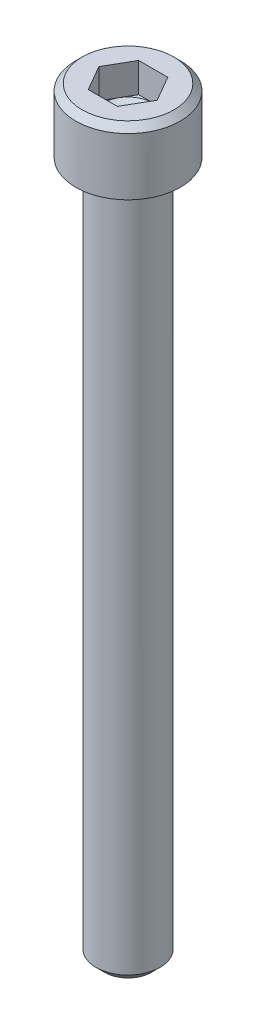
SolidWorks part; units mm, degrees
material "Alloy Steel"
ref_plane "Front Plane" through (0, 0, 0) normal (0, 0, 1) x (1, 0, 0)
ref_plane "Top Plane" through (0, 0, 0) normal (0, 1, 0) x (1, 0, 0)
ref_plane "Right Plane" through (0, 0, 0) normal (1, 0, 0) x (0, 0, -1)
sketch "Sketch1" plane through (0, 0, 0) normal (0, 0, 1) x (1, 0, 0)
  line L0 (2.8702, 3.5052) -> (0, 3.5052)
  line L1 (0, 3.5052) -> (0, 0)
  line L2 (0, 0) -> (2.8702, 0)
  line L3 (2.8702, 0) -> (2.8702, 3.5052)
  line L4 (0, 3.5052) -> (0, 0) construction
revolve "Revolve1" add sketch "Sketch1" angle 360 about L4 reverse direction yes
sketch "Sketch2" plane through (0, 0, 0) normal (0, -1, 0) x (1, 0, 0)
  circle A0 centre (0, 0) radius 1.7526
extrude "Boss-Extrude1" add sketch "Sketch2" along normal blind 38.1
sketch "Sketch3" plane through (0, 3.5052, 0) normal (0, 1, 0) x (-1, 0, 0)
  line L0 (-0.7992, 1.3843) -> (-1.5985, 0)
  line L1 (-1.5985, 0) -> (-0.7992, -1.3843)
  line L2 (-0.7992, -1.3843) -> (0.7992, -1.3843)
  line L3 (0.7992, -1.3843) -> (1.5985, 0)
  line L4 (1.5985, 0) -> (0.7992, 1.3843)
  line L5 (0.7992, 1.3843) -> (-0.7992, 1.3843)
extrude "Cut-Extrude1" cut sketch "Sketch3" against normal blind 1.6256
sketch "Sketch4" plane through (0, 0, 0) normal (0, 0, 1) x (1, 0, 0)
  line L0 (1.3843, 1.8796) -> (0, 1.8796)
  line L1 (0, 1.8796) -> (0, 1.0804)
  line L2 (0, 1.0804) -> (1.3843, 1.8796)
  line L3 (0, 1.8796) -> (0, 1.0803) construction
revolve "Cut-Revolve1" cut sketch "Sketch4" angle 360 about L3 reverse direction yes
chamfer "Chamfer1" distance 0.4724 angle 45 1 edges at (0, -38.1, -1.7526)
chamfer "Chamfer2" distance 0.3556 angle 45 1 edges at (0, 3.5052, -2.8702)
fillet "Fillet1" radius 0.254 1 edges at (0, 0, -1.7526) tangent propagation no
